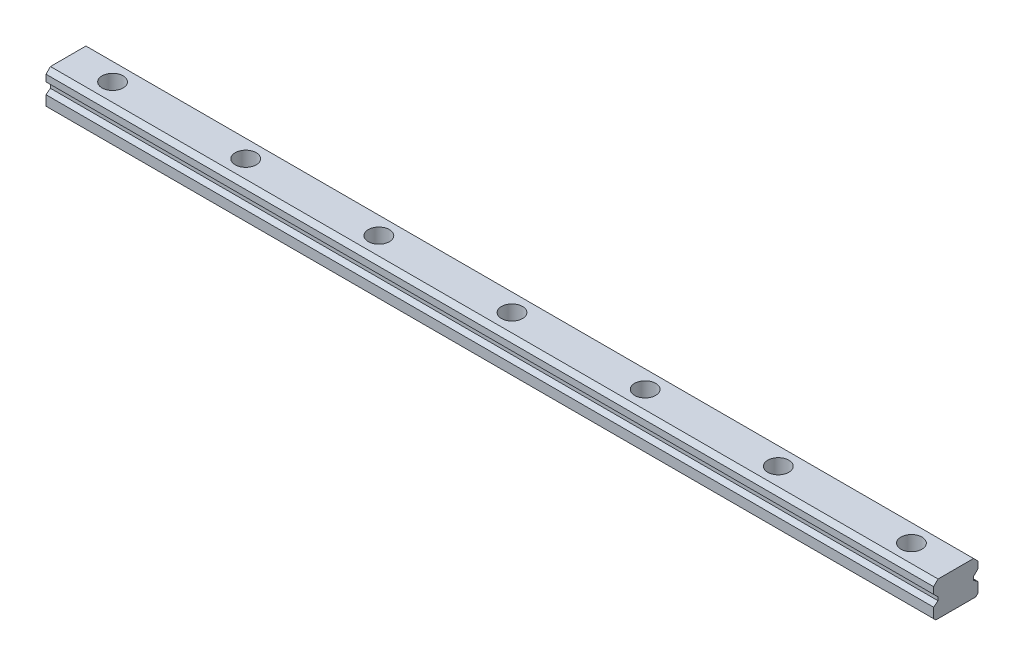
SolidWorks part; units mm, degrees
material "201 Annealed Stainless Steel (SS)"
ref_plane "Front Plane" through (0, 0, 0) normal (0, 0, 1) x (1, 0, 0)
ref_plane "Top Plane" through (0, 0, 0) normal (0, 1, 0) x (1, 0, 0)
ref_plane "Right Plane" through (0, 0, 0) normal (1, 0, 0) x (0, 0, -1)
sketch "Sketch1" plane through (0, 0, 0) normal (1, 0, 0) x (0, 0, -1)
  line L0 (0, 39.5089) -> (0, 0) construction
  line L1 (9, 0) -> (-9, 0)
  line L2 (-9, 0) -> (-10, 1)
  line L3 (-10, 1) -> (-10, 5.5)
  line L4 (-10, 5.5) -> (-8, 7)
  line L5 (-8, 7) -> (-8, 8.5)
  line L6 (-8, 8.5) -> (-10, 10.5)
  line L7 (-10, 10.5) -> (-10, 13.5)
  line L8 (-10, 13.5) -> (-8, 15.5)
  line L9 (-8, 15.5) -> (8, 15.5)
  line L10 (-18.0832, 7.75) -> (13.0406, 7.75) construction
  line L11 (-4.25, 15.5) -> (-4.25, 7) construction
  line L12 (-4.25, 7) -> (-3, 7) construction
  line L13 (-3, 7) -> (-3, 0) construction
  line L14 (4.25, 15.5) -> (4.25, 7) construction
  line L15 (4.25, 7) -> (3, 7) construction
  line L16 (3, 7) -> (3, 0) construction
  line L17 (9, 0) -> (10, 1)
  line L18 (10, 1) -> (10, 5.5)
  line L19 (10, 5.5) -> (8, 7)
  line L20 (8, 7) -> (8, 8.5)
  line L21 (8, 8.5) -> (10, 10.5)
  line L22 (10, 13.5) -> (8, 15.5)
  line L23 (10, 10.5) -> (10, 13.5)
  point P14 (-8, 7.75)
  point P32 (0, 15.5)
  dimension "D1" = 10
  dimension "D2" = 1
  dimension "D3" = 1
  dimension "D4" = 5.5
  dimension "D5" = 7.75
  dimension "D6" = 15.5
  dimension "D7" = 4.25
  dimension "D8" = 3
  dimension "D9" = 8.5
  dimension "D10" = 7
  dimension "D11" = 2
  dimension "D12" = 2
  dimension "D13" = 2
  dimension "D14" = 2
extrude "Boss-Extrude1" add sketch "Sketch1" along normal blind 400
sketch "Sketch2" plane through (0, 15.5, 0) normal (0, 1, 0) x (1, 0, 0)
  line L0 (0, 0) -> (400, 0) construction
  line L1 (0, 8) -> (0, -8) construction
  line L2 (400, 8) -> (400, -8) construction
  circle A0 centre (20, 0) radius 4.75
  dimension "D1" = 9.5
  dimension "D2" = 20
extrude "Cut-Extrude1" cut sketch "Sketch2" against normal blind 8.5
sketch "Sketch3" plane through (0, 7, 0) normal (0, 1, 0) x (1, 0, 0)
  circle A0 centre (20, 0) radius 3
  dimension "D1" = 6
extrude "Cut-Extrude2" cut sketch "Sketch3" against normal through all
pattern_linear "LPattern1" count 7 spacing 60 along (1, 0, 0) of "Cut-Extrude2", "Cut-Extrude1"
